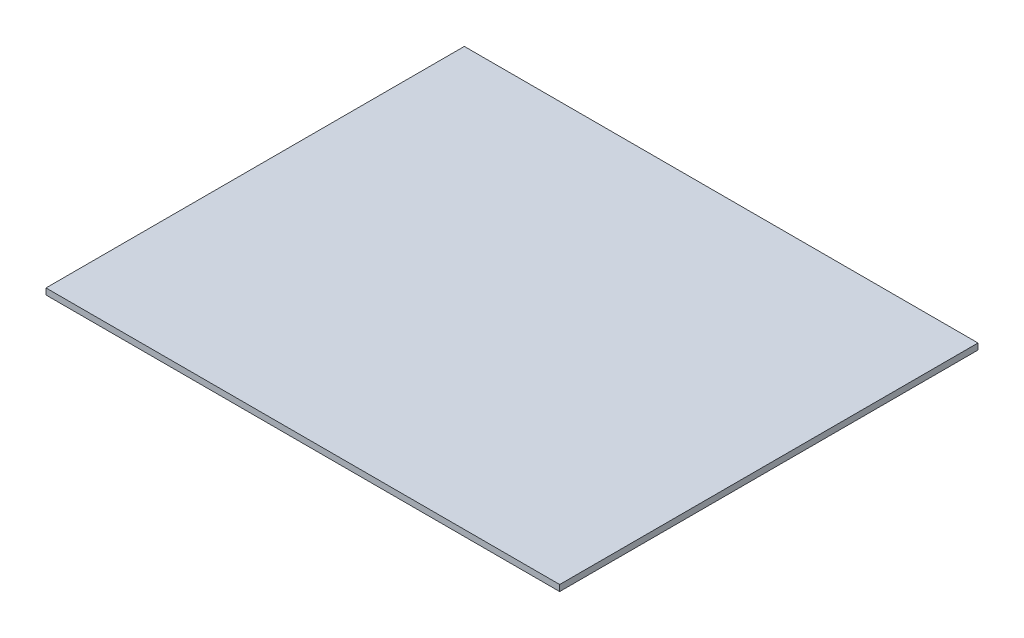
SolidWorks part; units mm, degrees
ref_plane "Front Plane" through (0, 0, 0) normal (0, 0, 1) x (1, 0, 0)
ref_plane "Top Plane" through (0, 0, 0) normal (0, 1, 0) x (1, 0, 0)
ref_plane "Right Plane" through (0, 0, 0) normal (1, 0, 0) x (0, 0, -1)
sketch "Sketch1" plane through (0, 0, 0) normal (0, 1, 0) x (1, 0, 0)
  line L0 (-62.5, -47) -> (-62.5, 47)
  line L1 (-60.5, -45) -> (60.5, -45)
  line L2 (-60.5, -45) -> (-60.5, 7)
  line L4 (60.5, -45) -> (60.5, 7)
  line L5 (-62.5, 47) -> (62.5, 47)
  line L6 (62.5, -47) -> (62.5, 47)
  line L7 (-62.5, -47) -> (62.5, -47)
  line L8 (-60.5, 7) -> (60.5, 7)
  line L9 (0, 0) -> (0, 7) construction
  line L10 (-60.5, -45) -> (-60.5, 45) construction
  line L11 (-60.5, 45) -> (60.5, 45) construction
  line L12 (60.5, -45) -> (60.5, 45) construction
  line L13 (-83.5, -68) -> (-83.5, 68)
  line L14 (-83.5, 68) -> (83.5, 68)
  line L15 (83.5, -68) -> (83.5, 68)
  line L16 (-83.5, -68) -> (83.5, -68)
  point P0 (0, 0)
  point P6 (0, -47)
  point P7 (62.5, 0)
  point P14 (0, 7)
  dimension "D1" = 94
  dimension "D2" = 125
  dimension "D4" = 40
  dimension "D3" = 2
  dimension "D5" = 21
extrude "Main" add sketch "Sketch1" along normal blind 10 contours L0 L7 L6 L5 L4 L1 L2 region at (0, 0, -21.9033)
ref_plane "BacklitPlane" through (0, 10, 0) normal (0, 1, 0) x (1, 0, 0)
extrude "MainFrontFace" add sketch "Sketch1<4>" along normal blind 2 from surface contours L13 L16 L15 L14 L7 L0 L5 L6 | L8 L2 L1 L4 | L0 L7 L6 L5 L2 L8 L4 L1 region at (0, 0, -21.9033) region at (0, 0, 19) region at (-81.3463, 0, 0) starting at plane "BacklitPlane"
sketch "Sketch1<4>" plane through (0, 0, 0) normal (0, 1, 0) x (1, 0, 0) same geometry as "Sketch1"
sketch "Sketch5" plane through (0, 0, 0) normal (0, -1, 0) x (1, 0, 0)
  circle A0 centre (-50, -35) radius 3.5
  dimension "D3" = 7
  dimension "D1" = 50
  dimension "D2" = 35
extrude "Notch" add sketch "Sketch5" along normal blind 4.2
sketch3d "3DSketch2"
  line L0 (-50, -4.2, -35) -> (-50, 0, -35) construction
  point P0 (-50, -4.2, -35)
ref_plane "Plane2" through (0, 0, -35) normal (0, 0, 1) x (1, 0, 0)
sketch "Sketch8" plane through (0, 0, -35) normal (0, 0, 1) x (1, 0, 0)
  line L0 (-50, -8.4) -> (-50, 0) construction
  line L1 (-53.5, 0) -> (-46.5, 0) construction
  line L2 (-43, -4.2) -> (-57, -4.2)
  arc A1 (-57, -4.2) -> (-43, -4.2) centre (-50, 2.9414) ccw
  point P7 (-50, -4.2)
  point P12 (-50, -4.2)
  dimension "D2" = 10
  dimension "D1" = 14
revolve "ActualNotch" add sketch "Sketch8" angle 360 about L0 region at (-50, -5.3587, -35)
mirror "Mirror1" about plane through (0, 0, 0) normal (1, 0, 0) of "ActualNotch", "Notch"
sketch "Sketch11" plane through (0, 0, 0) normal (0, -1, 0) x (1, 0, 0)
  line L0 (-62.5, 47) -> (-62.5, -47) construction
  line L1 (-60.5, 45) -> (-62.5, 45)
  line L2 (-60.5, 45) -> (-60.5, 39)
  line L3 (-60.5, 39) -> (-62.5, 39)
  line L4 (-62.5, 45) -> (-62.5, 39)
  line L5 (62.5, 47) -> (62.5, -47) construction
  line L6 (60.5, 45) -> (62.5, 45)
  line L7 (60.5, 45) -> (60.5, 39)
  line L8 (60.5, 39) -> (62.5, 39)
  line L9 (62.5, 45) -> (62.5, 39)
  dimension "D1" = 6
  dimension "D2" = 6
extrude "WireHoles" cut sketch "Sketch11" against normal up to surface (10 mm away) up to face at (0, 10, 0)
sketch "Sketch13" plane through (0, 10, 0) normal (0, -1, 0) x (1, 0, 0)
  line L0 (-62.5, 39) -> (-62.5, -47) construction
  line L1 (-62.5, -31.5) -> (-77.5, -31.5)
  line L2 (-62.5, -31.5) -> (-62.5, 23.5)
  line L3 (-62.5, 23.5) -> (-77.5, 23.5)
  line L4 (-77.5, -31.5) -> (-77.5, 23.5)
  line L5 (-62.5, -47) -> (62.5, -47) construction
  line L6 (-44, -47) -> (44, -47)
  line L7 (-44, -47) -> (-44, -62)
  line L8 (-44, -62) -> (44, -62)
  line L9 (44, -47) -> (44, -62)
  line L10 (62.5, 39) -> (62.5, -47) construction
  line L11 (62.5, -31.5) -> (77.5, -31.5)
  line L12 (62.5, -31.5) -> (62.5, 23.5)
  line L13 (62.5, 23.5) -> (77.5, 23.5)
  line L14 (77.5, -31.5) -> (77.5, 23.5)
  line L15 (-62.5, 47) -> (62.5, 47) construction
  line L16 (44, 47) -> (-44, 47)
  line L17 (44, 47) -> (44, 62)
  line L18 (44, 62) -> (-44, 62)
  line L19 (-44, 47) -> (-44, 62)
  point P24 (-62.5, -4)
  point P25 (-62.5, -4)
  point P26 (0, -47)
  point P27 (0, -47)
  dimension "D1" = 15
  dimension "D2" = 55
  dimension "D3" = 88
extrude "Ridges" add sketch "Sketch13" along normal blind 2
